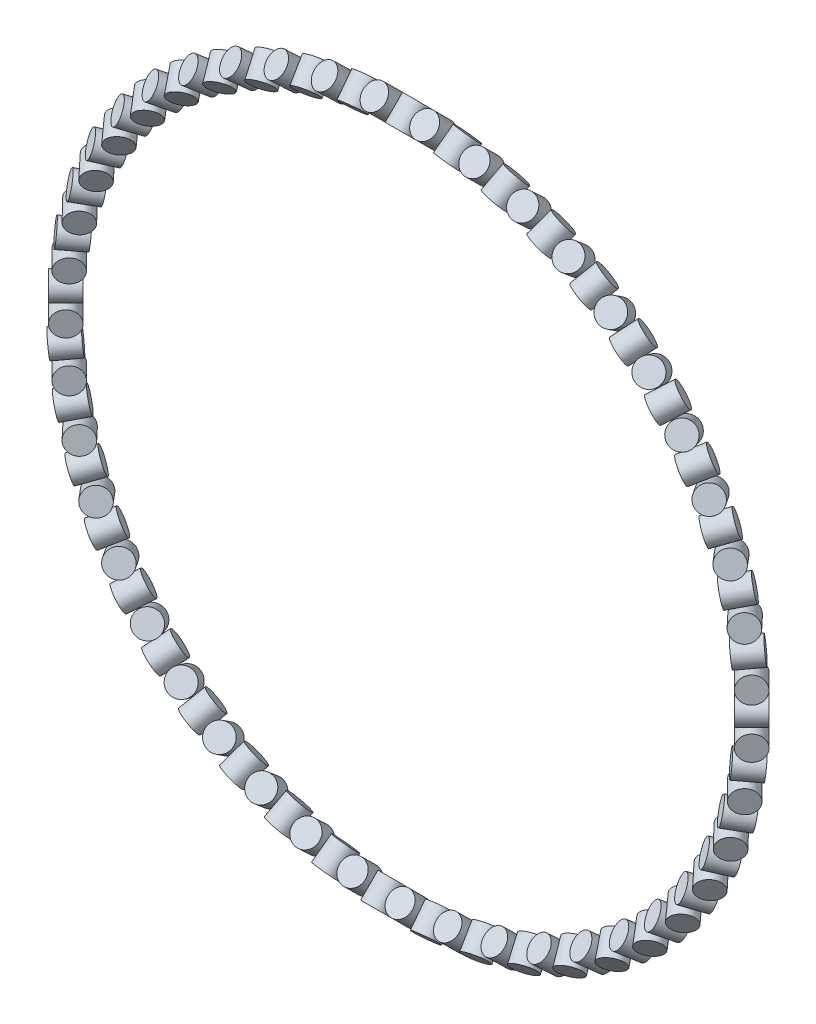
SolidWorks part; units mm, degrees
note: '?' marks a value the reader was unsure of.
ref_plane "前视基准面" through (0, 0, 0) normal (0, 0, 1) x (1, 0, 0)
ref_plane "上视基准面" through (0, 0, 0) normal (0, 1, 0) x (1, 0, 0)
ref_plane "右视基准面" through (0, 0, 0) normal (1, 0, 0) x (0, 0, -1)
sketch "草图1" plane through (0, 0, 0) normal (0, 0, 1) x (1, 0, 0)
  circle A0 centre (0, 0) radius 1
extrude "凸台-拉伸1" add sketch "草图1" along normal blind 2
move or copy body "实体-移动/复制1" bodies to move or copy 266 copy no rotation origin (0, 0, 1) rotation axis (1, 0, 0) rotation angle 45
move or copy body "实体-移动/复制2" bodies to move or copy 267 copy yes number of copies 1 translate (2, 0, 0)
move or copy body "实体-移动/复制3" bodies to move or copy 268 copy no rotation origin (0, 0, 1) rotation axis (1, 0, 0) rotation angle 90
ref_axis "基准轴1" through (0, 0, -0.8506) along (0, 0, 1)?
move or copy body "实体-移动/复制4" bodies to move or copy 267 269 copy no translate (0, 28, 0)
pattern_circular "阵列(圆周)1" count 44 over 360 about axis through (0, 0, 0) along (0, 0, 1)
